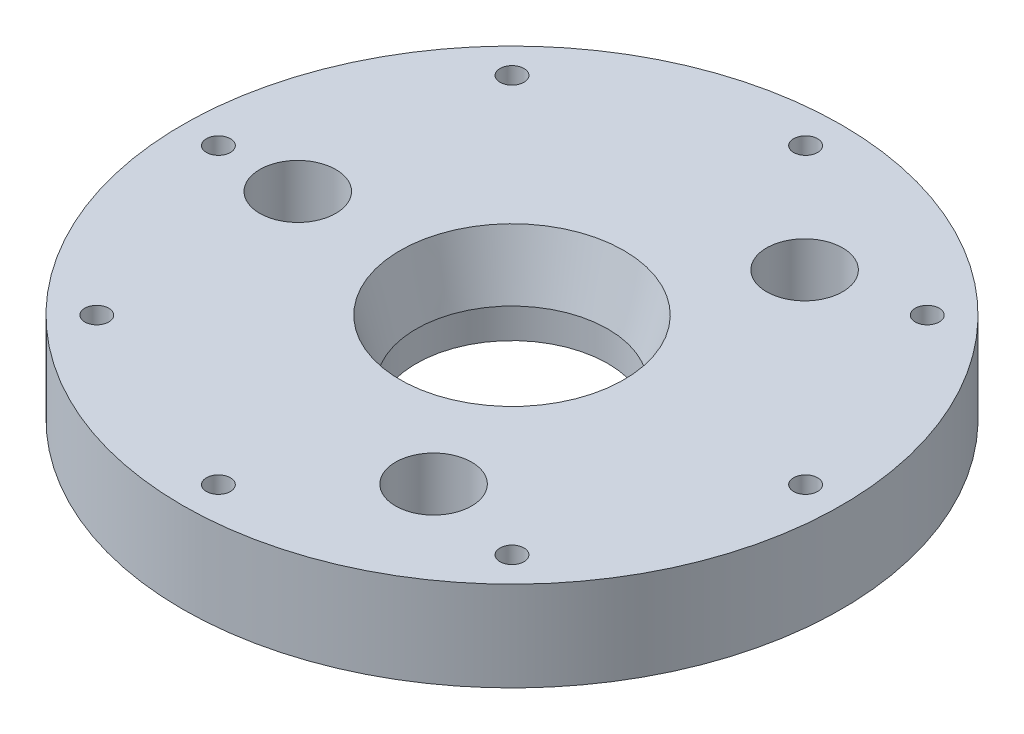
SolidWorks part; units mm, degrees
ref_plane "Front Plane" through (0, 0, 0) normal (0, 0, 1) x (1, 0, 0)
ref_plane "Top Plane" through (0, 0, 0) normal (0, 1, 0) x (1, 0, 0)
ref_plane "Right Plane" through (0, 0, 0) normal (1, 0, 0) x (0, 0, -1)
sketch "Sketch1" plane through (0, 0, 0) normal (0, 1, 0) x (1, 0, 0)
  circle A0 centre (0, 0) radius 55
  dimension "D1" = 110
extrude "Boss-Extrude1" add sketch "Sketch1" along normal blind 15 contours A0
sketch "Sketch5" plane through (0, 0, 0) normal (0, 0, 1) x (1, 0, 0)
  line L0 (0, 0) -> (0, 29.9809) construction
  line L1 (0, 0) -> (0, 15)
  line L2 (16, 5) -> (18.6795, 15)
  line L4 (55, 15) -> (-55, 15) construction
  line L5 (16, 5) -> (16, 0)
  line L6 (-55, 0) -> (55, 0) construction
  line L7 (0, 0) -> (16, 0)
  line L8 (18.6795, 15) -> (0, 15)
  line L9 (16, 0) -> (16, 15) construction
  dimension "D1" = 16
  dimension "D2" = 10
  dimension "D3" = 15
revolve "Cut-Revolve1" cut sketch "Sketch5" angle 360 about L0
sketch "Sketch6" plane through (0, 0, 0) normal (0, 1, 0) x (1, 0, 0)
  line L0 (0, 0) -> (49, 0) construction
  circle A0 centre (49, 0) radius 2
  dimension "D1" = 4
  dimension "D2" = 49
extrude "Cut-Extrude3" cut sketch "Sketch6" along normal through all
pattern_circular "CirPattern1" count 8 over 360 of "Cut-Extrude3"
sketch "Sketch7" plane through (0, 15, 0) normal (0, 1, 0) x (1, 0, 0)
  line L0 (0, 0) -> (17.875, 30.9604) construction
  line L1 (0, 0) -> (54.5383, 0) construction
  circle A0 centre (17.875, 30.9604) radius 6.35
  dimension "D1" = 12.7
  dimension "D2" = 35.75
  dimension "D3" = 60
extrude "Cut-Extrude4" cut sketch "Sketch7" against normal through all
pattern_circular "CirPattern2" count 3 over 360 of "Cut-Extrude4"
